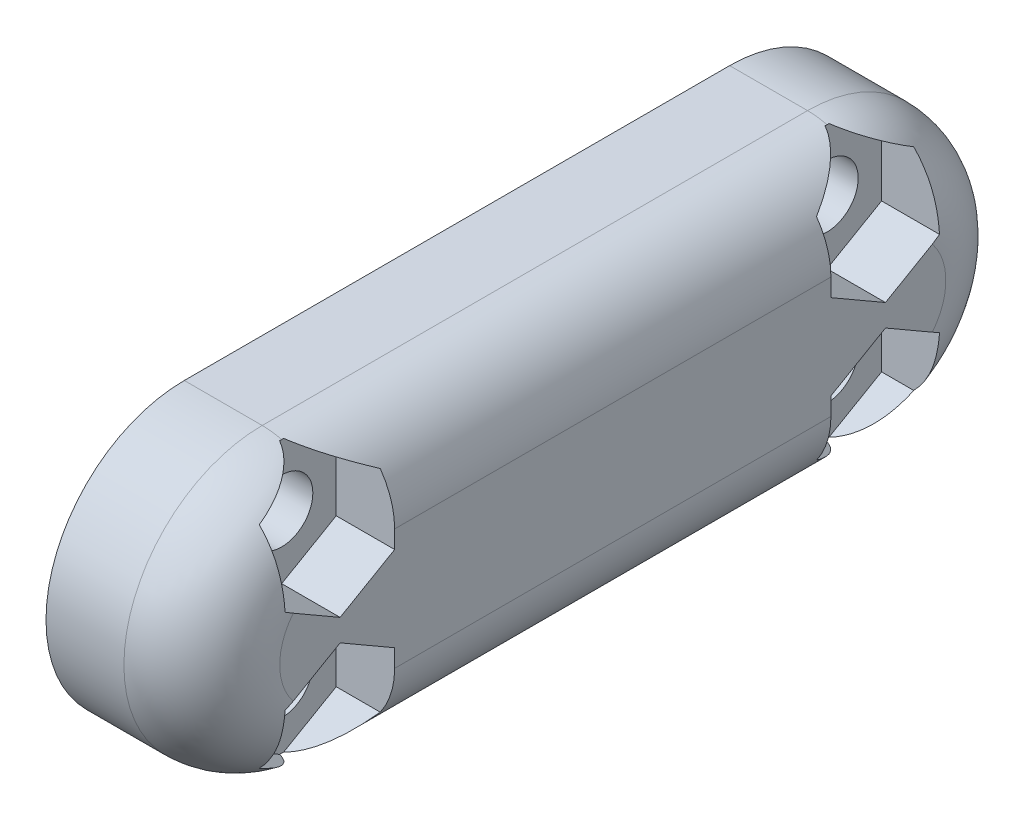
SolidWorks part; units mm, degrees
ref_plane "Front Plane" through (0, 0, 0) normal (0, 0, 1) x (1, 0, 0)
ref_plane "Top Plane" through (0, 0, 0) normal (0, 1, 0) x (1, 0, 0)
ref_plane "Right Plane" through (0, 0, 0) normal (1, 0, 0) x (0, 0, -1)
sketch "Sketch1" plane through (0, 0, 0) normal (1, 0, 0) x (0, 0, -1)
  line L0 (0, 2) -> (0, -2) construction
  line L1 (0, 5.6) -> (21, 5.6) construction
  line L2 (0, 5.6) -> (0, 2) construction
  line L3 (0, 2) -> (21, 2) construction
  line L4 (21, 5.6) -> (21, 2) construction
  line L5 (0, -2) -> (21, -2) construction
  line L6 (0, -2) -> (0, -5.6) construction
  line L7 (0, -5.6) -> (21, -5.6) construction
  line L8 (21, -2) -> (21, -5.6) construction
  line L9 (21, 2) -> (21, -2) construction
  point P8 (0, 0)
  dimension "D1" = 3.6
  dimension "D2" = 4
  dimension "D3" = 3.6
  dimension "D4" = 21
sketch "Sketch2" plane through (0, 0, 0) normal (1, 0, 0) x (0, 0, -1)
  line L0 (0, 5.6) -> (21, 5.6) construction
  line L1 (-3.5, 7.1) -> (24.5, 7.1)
  line L2 (-3.5, 7.1) -> (-3.5, -7.1) construction
  line L3 (-3.5, -7.1) -> (24.5, -7.1)
  line L4 (24.5, 7.1) -> (24.5, -7.1) construction
  line L5 (0, -5.6) -> (21, -5.6) construction
  line L6 (0, 5.6) -> (0, 2) construction
  line L8 (21, 5.6) -> (21, 2) construction
  line L9 (-3.5, 3.8) -> (24.5, 3.8) construction
  line L10 (24.5, -3.8) -> (-3.5, -3.8) construction
  line L11 (0, -2) -> (0, -5.6) construction
  arc A0 (-3.5, 7.1) -> (-3.5, -7.1) centre (-3.5, 0) ccw
  arc A1 (24.5, 7.1) -> (24.5, -7.1) centre (24.5, 0) cw
  point P20 (0, -3.8)
  point P21 (0, 3.8)
  dimension "D1" = 1.5
  dimension "D2" = 1.5
  dimension "D3" = 3.5
  dimension "D4" = 3.5
extrude "Boss-Extrude1" add sketch "Sketch2" along normal blind 8
sketch "Sketch4" plane through (0, 0, 0) normal (0, 0, 1) x (1, 0, 0)
  line L0 (0, 5.6) -> (0, 2) construction
  line L1 (0, 2) -> (2, 2)
  line L2 (0, 2) -> (0, -2)
  line L3 (0, -2) -> (2, -2)
  line L4 (2, 2) -> (2, -2)
  point P6 (0, 0)
  dimension "D1" = 2
  dimension "D2" = 4
extrude "Cut-Extrude5" cut sketch "Sketch4" against normal up to next
sketch "Sketch5" plane through (0, 0, 0) normal (1, 0, 0) x (0, 0, -1)
  line L1 (21, 5.6) -> (0, 5.6)
  line L2 (21, 5.6) -> (21, 2)
  line L3 (21, 2) -> (0, 2)
  line L4 (0, 5.6) -> (0, 2)
  line L5 (21, -2) -> (0, -2)
  line L6 (21, -2) -> (21, -5.6)
  line L7 (21, -5.6) -> (0, -5.6)
  line L8 (0, -2) -> (0, -5.6)
extrude "Cut-Extrude2" cut sketch "Sketch5" along normal blind 6.75
sketch "Sketch6" plane through (8, 0, 0) normal (1, 0, 0) x (0, 0, -1)
  circle A0 centre (-3.5, 3.8) radius 1.6
  circle A1 centre (-3.5, -3.8) radius 1.6
  circle A2 centre (24.5, 3.8) radius 1.6
  circle A3 centre (24.5, -3.8) radius 1.6
  dimension "D1" = 3.2
extrude "Cut-Extrude3" cut sketch "Sketch6" along direction (1, 0, 0) on the side against the normal up to next (8 mm away)
sketch "Sketch7" plane through (8, 0, 0) normal (1, 0, 0) x (0, 0, -1)
  line L1 (-0.7, 2.1834) -> (-0.7, 5.4166)
  line L2 (-0.7, 5.4166) -> (-3.5, 7.0332)
  line L3 (-3.5, 7.0332) -> (-6.3, 5.4166)
  line L4 (-6.3, 5.4166) -> (-6.3, 2.1834)
  line L5 (-6.3, 2.1834) -> (-3.5, 0.5668)
  line L6 (-3.5, 0.5668) -> (-0.7, 2.1834)
  line L7 (21.7, 5.4166) -> (21.7, 2.1834)
  line L8 (21.7, 2.1834) -> (24.5, 0.5668)
  line L9 (24.5, 0.5668) -> (27.3, 2.1834)
  line L10 (27.3, 2.1834) -> (27.3, 5.4166)
  line L11 (27.3, 5.4166) -> (24.5, 7.0332)
  line L12 (24.5, 7.0332) -> (21.7, 5.4166)
  line L13 (21.7, -2.1834) -> (21.7, -5.4166)
  line L14 (21.7, -5.4166) -> (24.5, -7.0332)
  line L15 (24.5, -7.0332) -> (27.3, -5.4166)
  line L16 (27.3, -5.4166) -> (27.3, -2.1834)
  line L17 (27.3, -2.1834) -> (24.5, -0.5668)
  line L18 (24.5, -0.5668) -> (21.7, -2.1834)
  line L19 (-3.5, -7.0332) -> (-0.7, -5.4166)
  line L20 (-0.7, -5.4166) -> (-0.7, -2.1834)
  line L21 (-0.7, -2.1834) -> (-3.5, -0.5668)
  line L22 (-3.5, -0.5668) -> (-6.3, -2.1834)
  line L23 (-6.3, -2.1834) -> (-6.3, -5.4166)
  line L24 (-6.3, -5.4166) -> (-3.5, -7.0332)
  line L26 (-3.5, 7.1) -> (-3.5, -7.1) construction
  line L27 (24.5, 7.1) -> (24.5, -7.1) construction
  circle A0 centre (-3.5, 3.8) radius 2.8 construction
  circle A1 centre (24.5, 3.8) radius 2.8 construction
  circle A2 centre (24.5, -3.8) radius 2.8 construction
  circle A3 centre (-3.5, -3.8) radius 2.8 construction
  point P27 (0, 0)
  point P35 (-3.3954, 0.5911)
  point P37 (0, 0)
  point P39 (0, 0)
  point P40 (0, 0)
  point P41 (0, 0)
  point P42 (0, 0)
  point P44 (-2.8849, -3.5335)
  point P46 (24, 3.8)
  point P47 (-2.6798, -7.0173)
  point P48 (0, 0)
  point P51 (0, 0)
  dimension "D1" = 5.6
extrude "Cut-Extrude4" cut sketch "Sketch7" against normal blind 3
fillet "Fillet1" radius 4 4 edges at (8, 7.1, -10.5) (8, 0, -31.6) (8, -7.1, -10.5) (8, 0, 10.6)
